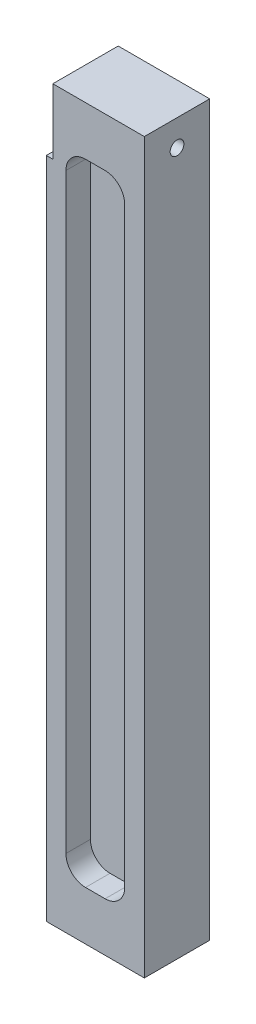
SolidWorks part; units mm, degrees
material "6061 合金"
ref_plane "前视基准面" through (0, 0, 0) normal (0, 0, 1) x (1, 0, 0)
ref_plane "上视基准面" through (0, 0, 0) normal (0, 1, 0) x (1, 0, 0)
ref_plane "右视基准面" through (0, 0, 0) normal (1, 0, 0) x (0, 0, -1)
sketch "草图1" plane through (0, 0, 0) normal (0, 1, 0) x (1, 0, 0)
  line L1 (-15, -10) -> (15, -10)
  line L2 (-15, -10) -> (-15, 10)
  line L3 (-15, 10) -> (15, 10)
  line L4 (15, -10) -> (15, 10)
  line L5 (-15, -10) -> (15, 10) construction
  line L6 (-15, 10) -> (15, -10) construction
  point P0 (0, 0)
  dimension "D1" = 20
  dimension "D2" = 30
extrude "凸台-拉伸1" add sketch "草图1" along normal blind 223
sketch "草图2" plane through (0, 0, -10) normal (0, 0, 1) x (1, 0, 0)
  line L0 (0, 0) -> (0, 211.9387) construction
  line L1 (-15, 0) -> (15, 0) construction
  line L2 (-3, 15) -> (3, 15)
  line L3 (-9, 21) -> (-9, 202)
  line L7 (-3, 208) -> (3, 208)
  line L8 (9, 21) -> (9, 202)
  line L9 (-9, 15) -> (9, 208) construction
  line L10 (-9, 208) -> (9, 15) construction
  line L11 (-15, 223) -> (15, 223) construction
  arc A0 (3, 15) -> (9, 21) centre (3, 21) ccw
  arc A1 (-3, 15) -> (-9, 21) centre (-3, 21) cw
  arc A2 (3, 208) -> (9, 202) centre (3, 202) cw
  arc A3 (-9, 202) -> (-3, 208) centre (-3, 202) cw
  point P3 (0, 111.5)
  dimension "D4" = 6
  dimension "D1" = 18
  dimension "D2" = 15
  dimension "D3" = 15
extrude "切除-拉伸1" cut sketch "草图2" along normal offset from surface (7.5 mm away) 2.5 up to plane "前视基准面"
mirror "镜向1" about plane through (0, 0, 0) normal (0, 0, 1) of "切除-拉伸1"
hole_wizard "M5 螺纹孔1" positions "草图4" profile "草图3" tap size "M5" standard "GB"
sketch "草图4" plane through (0, 0, 0) normal (0, -1, 0) x (-1, 0, 0)
  line L0 (0, 0) -> (0, 7.831) construction
  line L2 (-15, -10) -> (-15, 10) construction
  point P0 (8, 0)
  point P2 (-8, 0)
  dimension "D1" = 7
sketch "草图3" plane through (-8, 0, 0) normal (1, 0, 0) x (0, 0, -1)
  line L0 (0, 0) -> (0, 15.2618)
  line L1 (0, 15.2618) -> (2.1, 14)
  line L2 (2.1, 14) -> (2.1, 0)
  line L5 (2.1, 0) -> (0, 0)
  line L10 (0, 15.2618) -> (-2.1, 14) construction
  line L11 (0, -6.35) -> (0, 107.95) construction
  dimension "螺纹孔钻头直径" = 4.2
  dimension "螺纹孔钻头深度" = 14
  dimension "导头角度" = 118
cosmetic thread "孔螺蚊线1" parameters "D1"=10, "D2"=5
cosmetic thread "孔螺蚊线2" parameters "D1"=10, "D2"=5
hole_wizard "M5 螺纹孔2" positions "草图6" profile "草图5" tap size "M5" standard "GB" end condition up to next
sketch "草图6" plane through (15, 0, 0) normal (1, 0, 0) x (0, 0, -1)
  line L0 (-10, 223) -> (10, 223) construction
  point P0 (0, 215)
  dimension "D1" = 8
sketch "草图5" plane through (15, 215, 0) normal (0, 1, 0) x (0, 0, -1)
  line L0 (0, 0) -> (0, 30)
  line L1 (0, 30) -> (2.1, 30)
  line L2 (2.1, 30) -> (2.1, 0)
  line L5 (2.1, 0) -> (0, 0)
  line L11 (0, -6.35) -> (0, 107.95) construction
  dimension "通孔螺纹孔钻头直径" = 4.2
  dimension "通孔螺纹孔钻头深度" = 30
cosmetic thread "孔螺蚊线3" parameters "D2"=5
sketch "草图7" plane through (0, 0, 10) normal (0, 0, -1) x (-1, 0, 0)
  line L0 (13, 223) -> (13, 203)
  line L1 (-15, 223) -> (15, 223) construction
  line L2 (13, 203) -> (15, 203)
  line L4 (15, 223) -> (15, 0) construction
  dimension "D1" = 2
  dimension "D2" = 20
extrude "切除-拉伸2" cut sketch "草图7" along normal through all
